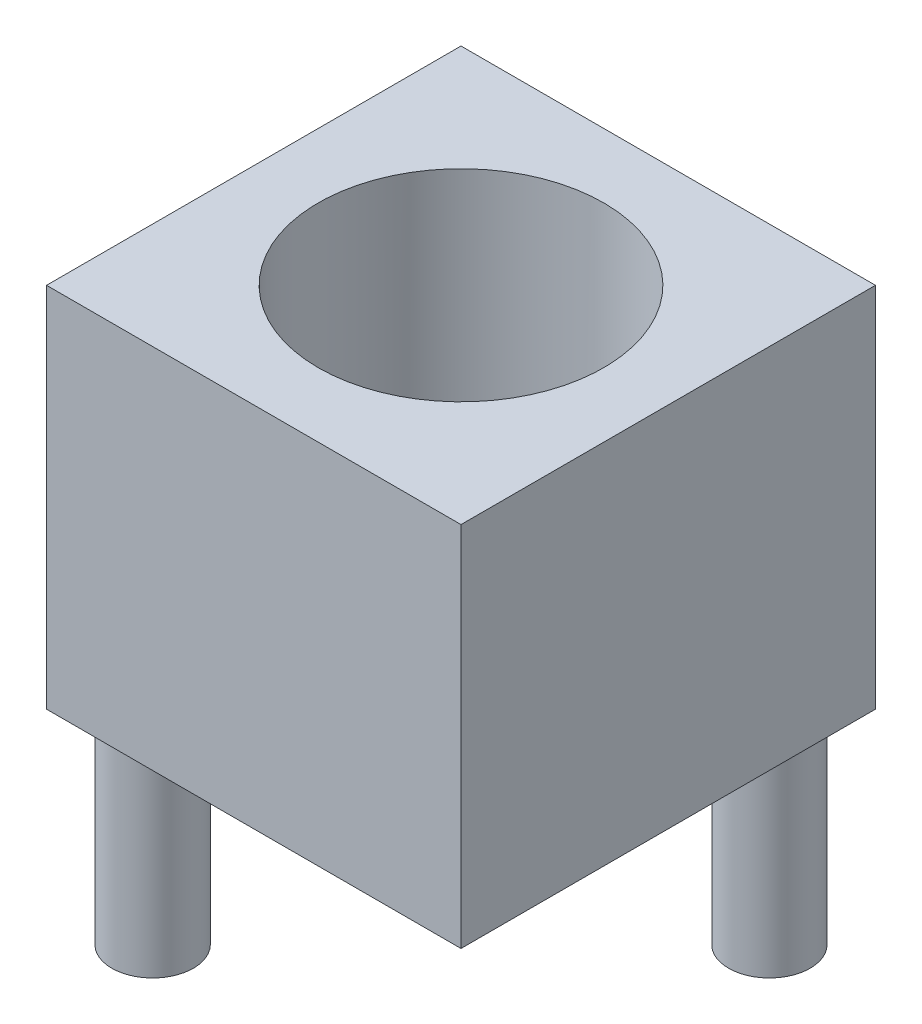
SolidWorks part; units mm, degrees
material "PPE"
ref_plane "Front Plane" through (0, 0, 0) normal (0, 0, 1) x (1, 0, 0)
ref_plane "Top Plane" through (0, 0, 0) normal (0, 1, 0) x (1, 0, 0)
ref_plane "Right Plane" through (0, 0, 0) normal (1, 0, 0) x (0, 0, -1)
sketch "Sketch1" plane through (0, 0, 0) normal (0, 1, 0) x (1, 0, 0)
  line L1 (-2.54, 2.54) -> (2.54, 2.54)
  line L2 (-2.54, 2.54) -> (-2.54, -2.54)
  line L3 (-2.54, -2.54) -> (2.54, -2.54)
  line L4 (2.54, 2.54) -> (2.54, -2.54)
  line L5 (-2.54, 2.54) -> (2.54, -2.54) construction
  line L6 (-2.54, -2.54) -> (2.54, 2.54) construction
  line L7 (-2, 1.25) -> (2, 1.25)
  line L8 (-2, 1.25) -> (-2, -1.25)
  line L9 (-2, -1.25) -> (2, -1.25)
  line L10 (2, 1.25) -> (2, -1.25)
  line L11 (-2, 1.25) -> (2, -1.25) construction
  line L12 (-2, -1.25) -> (2, 1.25) construction
  circle A0 centre (0, 0) radius 1.75
  circle A1 centre (-1.89, -1.89) radius 0.5
  circle A2 centre (1.89, 1.89) radius 0.5
  point P0 (0, 0)
  point P6 (0, 0)
  dimension "D4" = 3.5
  dimension "D6" = 1
  dimension "D1" = 5.08
  dimension "D2" = 2.5
  dimension "D3" = 4
  dimension "D5" = 1.89
extrude "Boss-Extrude1" add sketch "Sketch1" along normal blind 2 contours L4 L1 L2 L3 A0 L7 L10 L9 L8 A1 A2 | L9 A0 | L7 A0 | A1 | A2 region at (0, 0, -2.4682) region at (0, 0, -1.4527) region at (0, 0, 1.4527) region at (-1.89, 0, 1.89) region at (1.89, 0, -1.89)
sketch "Sketch2" plane through (0, 2, 0) normal (0, 1, 0) x (1, 0, 0)
  line L0 (-2.54, 2.54) -> (2.54, 2.54) construction
  line L1 (-2.54, 2.54) -> (-2.54, -2.54) construction
  line L2 (2.54, 2.54) -> (2.54, -2.54) construction
  line L3 (-2.54, 2.54) -> (2.54, 2.54)
  line L4 (2.54, -2.54) -> (2.54, 2.54)
  line L5 (2.54, 2.54) -> (-2.54, 2.54)
  line L6 (-2.54, 2.54) -> (-2.54, -2.54)
  line L7 (-2.54, -2.54) -> (2.54, -2.54)
  line L8 (2.54, -2.54) -> (2.54, 2.54)
  line L9 (2.54, 2.54) -> (-2.54, 2.54)
  line L10 (-2.54, 2.54) -> (-2.54, -2.54)
  line L11 (-2.54, -2.54) -> (2.54, -2.54)
  line L12 (-2.54, 2.54) -> (-2.54, -2.54)
  line L13 (2.54, 2.54) -> (2.54, -2.54)
  circle A0 centre (0, 0) radius 1.75 construction
  circle A1 centre (0, 0) radius 1.75
  line M5 (2.54, -2.54) -> (2.54, 2.54)
  line M6 (2.54, 2.54) -> (-2.54, 2.54)
  line M7 (-2.54, 2.54) -> (-2.54, -2.54)
  line M8 (-2.54, -2.54) -> (2.54, -2.54)
  line M9 (-2, -1.25) -> (-2, 1.25)
  line M10 (-2, 1.25) -> (2, 1.25)
  line M11 (2, 1.25) -> (2, -1.25)
  line M12 (2, -1.25) -> (-2, -1.25)
  dimension "D1" = 0
extrude "Boss-Extrude2" add sketch "Sketch2" along normal blind 2.5 contours A1 M8 M5 M6 M7 M10 M11 M12 M9 | A1 M10 M9 M12 | A1 M12 M11 M10 region at (0, 2, -2.4682) region at (1.7655, 2, 0) region at (-1.7655, 2, 0)
extrude "Boss-Extrude3" add sketch "Sketch1<3>" against normal blind 2.5 contours A1 | A2 region at (-1.89, 0, 1.89) region at (1.89, 0, -1.89)
sketch "Sketch1<3>" plane through (0, 0, 0) normal (0, 1, 0) x (1, 0, 0) same geometry as "Sketch1"
